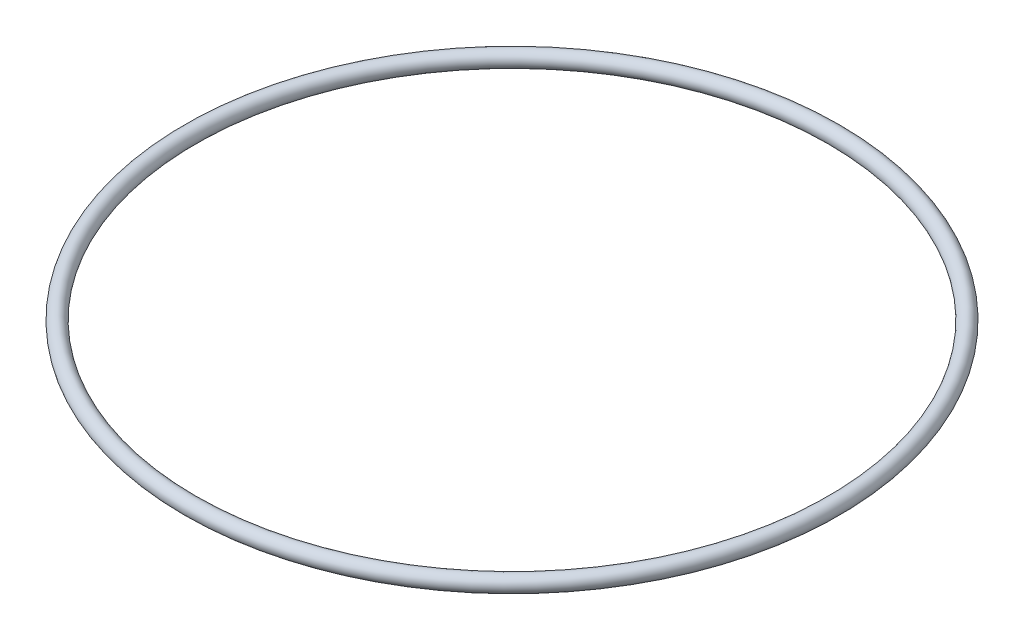
SolidWorks part; units mm, degrees
ref_plane "Front Plane" through (0, 0, 0) normal (0, 0, 1) x (1, 0, 0)
ref_plane "Top Plane" through (0, 0, 0) normal (0, 1, 0) x (1, 0, 0)
ref_plane "Right Plane" through (0, 0, 0) normal (1, 0, 0) x (0, 0, -1)
sketch "Sketch1" plane through (0, 0, 0) normal (1, 0, 0) x (0, 0, -1)
  line L0 (0, 0) -> (-61.5, 0) construction
  line L1 (0, 0) -> (0, 30.901) construction
  circle A0 centre (-61.5, 0) radius 1.5
  dimension "D1" = 3
  dimension "D2" = 61.5
revolve "Revolve1" add sketch "Sketch1" angle 360 about L1
ref_axis "Axis1" through (0, 32.521, 0) along (0, -1, 0)
